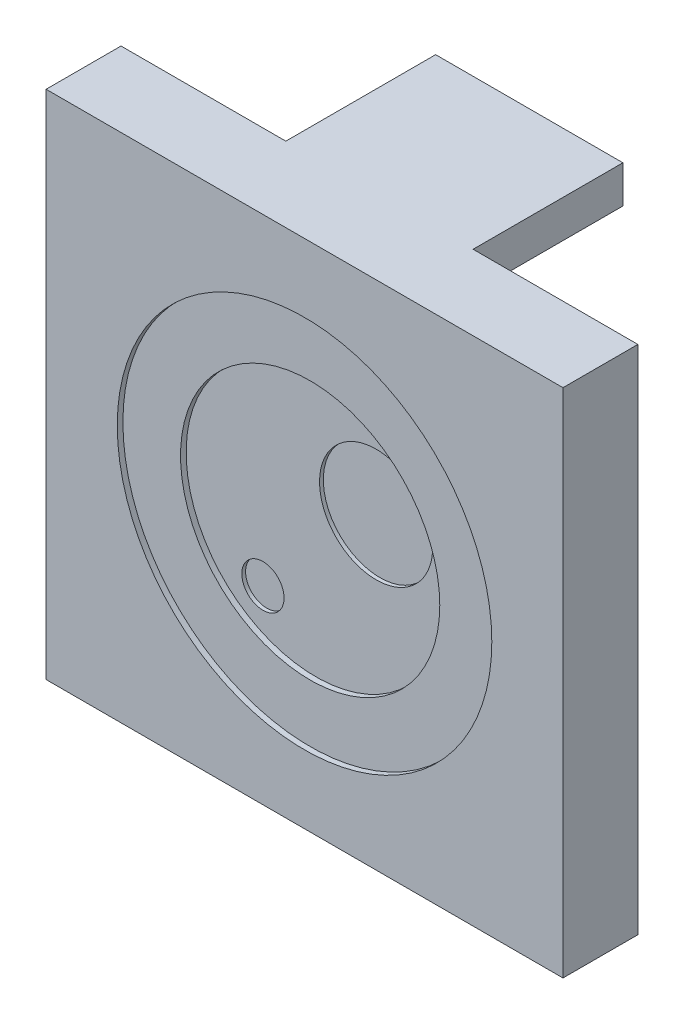
SolidWorks part; units mm, degrees
ref_plane "前视基准面" through (0, 0, 0) normal (0, 0, 1) x (1, 0, 0)
ref_plane "上视基准面" through (0, 0, 0) normal (0, 1, 0) x (1, 0, 0)
ref_plane "右视基准面" through (0, 0, 0) normal (1, 0, 0) x (0, 0, -1)
sketch "草图1" plane through (0, 0, 0) normal (0, 0, 1) x (1, 0, 0)
  line L1 (-13.8, -13.65) -> (13.8, -13.65)
  line L2 (-13.8, -13.65) -> (-13.8, 13.65)
  line L3 (-13.8, 13.65) -> (13.8, 13.65)
  line L4 (13.8, -13.65) -> (13.8, 13.65)
  line L5 (-13.8, -13.65) -> (13.8, 13.65) construction
  line L6 (-13.8, 13.65) -> (13.8, -13.65) construction
  point P0 (0, 0)
  dimension "D1" = 27.6
  dimension "D2" = 27.3
extrude "凸台-拉伸1" add sketch "草图1" along normal blind 4
sketch "草图2" plane through (0, 0, 0) normal (0, 0, 1) x (1, 0, 0)
  line L0 (0, 0) -> (0, -26.9182) construction
  line L1 (0, 0) -> (0, -24.1929) construction
  circle A0 centre (0, 0) radius 10
  circle A4 centre (0, 0) radius 6.9217
  circle A5 centre (-2.8212, -4.1281) radius 1.1273
  circle A6 centre (3.223, 2.1979) radius 3.0206
  circle A7 centre (0, 0) radius 3.9011 construction
  dimension "D2" = 13.8433
  dimension "D3" = 6.0411
  dimension "D4" = 2.2547
  dimension "D1" = 10
  dimension "D5" = 4.1281
  dimension "D6" = 2.8212
  dimension "D7" = 3.223
extrude "切除-拉伸1" cut sketch "草图2" against normal blind 0.3 from offset 4 contours A0
extrude "切除-拉伸7" cut sketch "草图2<3>" against normal blind 0.6 from offset 4 contours A4
sketch "草图2<3>" plane through (0, 0, 0) normal (0, 0, 1) x (1, 0, 0) same geometry as "草图2"
extrude "切除-拉伸8" cut sketch "草图2<5>" against normal blind 0.8 from offset 4 contours A6 | A5
sketch "草图2<5>" plane through (0, 0, 0) normal (0, 0, 1) x (1, 0, 0) same geometry as "草图2"
sketch "草图3" plane through (0, 0, 0) normal (0, 0, -1) x (-1, 0, 0)
  line L0 (-13.8, 13.65) -> (13.8, 13.65) construction
  line L2 (-5, 13.65) -> (-5, 11.65)
  line L3 (-5, 11.65) -> (5, 11.65)
  line L4 (5, 13.65) -> (5, 11.65)
  line L5 (0, 0) -> (0, 22.5913) construction
  line L7 (-5, 13.65) -> (5, 13.65)
  point P0 (0, 13.65)
  dimension "D1" = 10
  dimension "D2" = 2
extrude "凸台-拉伸2" add sketch "草图3" along normal blind 8
